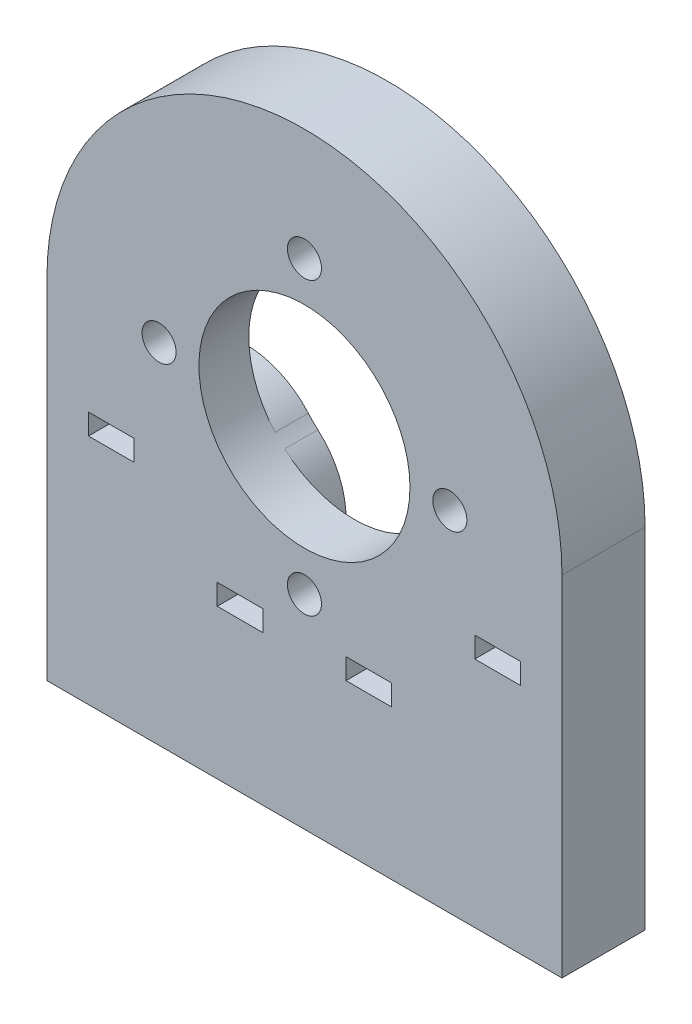
SolidWorks part; units mm, degrees
ref_plane "Front Plane" through (0, 0, 0) normal (1, 0, 0) x (0, 1, 0)
ref_plane "Top Plane" through (0, 0, 0) normal (0, 0, 1) x (0, 1, 0)
ref_plane "Right Plane" through (0, 0, 0) normal (0, 1, 0) x (-1, 0, 0)
sketch "Sketch1" plane through (0, 0, 0) normal (0, 0, 1) x (0, 1, 0)
  line L0 (0, 0) -> (42, 0) construction
  line L1 (0, 31) -> (0, -31)
  line L2 (0, 31) -> (42, 31)
  line L3 (0, -31) -> (42, -31)
  circle A0 centre (42, 0) radius 12.7021
  arc A1 (42, -31) -> (42, 31) centre (42, 0) ccw
  circle A2 centre (42, 0) radius 17.5
  circle A3 centre (59.5, 0) radius 2.05
  circle A4 centre (59.5, 0) radius 5
  circle A5 centre (42, -17.5) radius 5
  circle A6 centre (42, -17.5) radius 2.05
  circle A7 centre (24.5, 0) radius 5
  circle A8 centre (24.5, 0) radius 2.05
  circle A9 centre (42, 17.5) radius 5
  circle A10 centre (42, 17.5) radius 2.05
  point P7 (0, 0)
  dimension "D3" = 35
  dimension "D4" = 4.1
  dimension "D5" = 10
  dimension "D1" = 42
  dimension "D2" = 62
  dimension "D6" = 4
extrude "Boss-Extrude1" add sketch "Sketch1" along normal blind 10 contours L3 A1 L2 L1 A7 A2 A9 A4 A5 | L0 A7 A2 A8 | A8 L0 A2 | A7 L0 A8 A2 | L0 A8 A2 | A9 A2 A7 A0 | A10 A2 A9 A0 | A9 A0 A4 A2 | A2 A4 A0 A3 | A5 A2 A4 A0 | A6 A2 A5 A0 | A7 A2 A5 A0 | A6 A2 A5 | A2 A6 | A2 A6 | L0 A8 A2 A7 A0 | A2 L0 A8 | L0 A2 A8 | A8 L0 A0 A7 A2 | A2 A3 | A2 A3 | A2 A4 A3 | A2 A10 | A10 A2 A9 | A2 A10 region at (-2.4725, 22.2907, 0) region at (2.4725, 22.2907, 0) region at (-15.5, 0.9578, 0) region at (-0.8862, 23.6519, 0) region at (0.8862, 23.6519, 0) region at (-2.2829, 27.0064, 0) region at (-10.1867, 31.8133, 0) region at (10.1867, 31.8133, 0) region at (2.2829, 27.0064, 0) region at (-0.853, 25.3913, 0) region at (0.853, 25.3913, 0) region at (-19.7093, 42, 0) region at (-14.9936, 42, 0) region at (14.9936, 42, 0) region at (19.7093, 42, 0) region at (-18.3481, 42, 0) region at (-16.6087, 42, 0) region at (16.6087, 42, 0) region at (18.3481, 42, 0) region at (-10.1867, 52.1867, 0) region at (10.1867, 52.1867, 0) region at (0, 61.7093, 0) region at (0, 56.9936, 0) region at (0, 60.3481, 0) region at (0, 58.6087, 0)
extrude "Cut-Extrude1" cut sketch "Sketch1<3>" along normal blind 4 contours A7 | A9 | A4 | A5
sketch "Sketch1<3>" plane through (0, 0, 0) normal (0, 0, 1) x (0, 1, 0) same geometry as "Sketch1"
extrude "Cut-Extrude3" cut sketch "Sketch1<4>" along normal through all and the other way through all contours A6 | A3 | A10 | A8
sketch "Sketch1<4>" plane through (0, 0, 0) normal (0, 0, 1) x (0, 1, 0) same geometry as "Sketch1"
fillet "Fillet1" radius 10 8 edges at (-1.1976, 29.3545, 2) (1.1976, 29.3545, 2) (-12.6455, 40.8024, 2) (-12.6455, 43.1976, 2) (-1.1976, 54.6455, 2) (1.1976, 54.6455, 2) (12.6455, 43.1976, 2) (12.6455, 40.8024, 2)
sketch "Sketch2" plane through (0, 0, 0) normal (0, -1, 0) x (1, 0, 0)
  line L0 (-31, 5) -> (-23.25, 5) construction
  line L1 (-31, 10) -> (-31, 0) construction
  line L2 (-23.25, 5) -> (-23.25, 3.0468) construction
  line L3 (-22.3323, 3.6894) -> (-23.25, 3.0468)
  line L4 (-24.1677, 3.6894) -> (-23.25, 3.0468)
  line L5 (-8.6677, 3.6894) -> (-7.75, 3.0468)
  line L6 (-6.8323, 3.6894) -> (-7.75, 3.0468)
  line L7 (6.8323, 3.6894) -> (7.75, 3.0468)
  line L8 (8.6677, 3.6894) -> (7.75, 3.0468)
  line L9 (22.3323, 3.6894) -> (23.25, 3.0468)
  line L10 (24.1677, 3.6894) -> (23.25, 3.0468)
  arc A0 (-22.3323, 3.6894) -> (-24.1677, 3.6894) centre (-23.25, 5) ccw
  arc A1 (-6.8323, 3.6894) -> (-8.6677, 3.6894) centre (-7.75, 5) ccw
  arc A2 (8.6677, 3.6894) -> (6.8323, 3.6894) centre (7.75, 5) ccw
  arc A3 (24.1677, 3.6894) -> (22.3323, 3.6894) centre (23.25, 5) ccw
  point P4 (-23.25, 6.9532)
  point P8 (-22.9883, 3.0644)
  dimension "D2" = 3.2
  dimension "D1" = 7.75
  dimension "D3" = 55
  dimension "D4" = 4
sketch "Sketch3" plane through (0, 0, 10) normal (0, 0, 1) x (1, 0, 0)
  line L0 (-23.25, 28) -> (-23.25, 0)
  line L1 (-26, 30.5) -> (-20.5, 30.5)
  line L2 (-26, 30.5) -> (-26, 28)
  line L3 (-26, 28) -> (-20.5, 28)
  line L4 (-20.5, 30.5) -> (-20.5, 28)
  line L5 (-26, 30.5) -> (-20.5, 28) construction
  line L6 (-26, 28) -> (-20.5, 30.5) construction
  line L7 (-10.5, 20.5) -> (-5, 20.5)
  line L8 (-10.5, 20.5) -> (-10.5, 18)
  line L9 (-10.5, 18) -> (-5, 18)
  line L10 (-5, 20.5) -> (-5, 18)
  line L11 (-10.5, 20.5) -> (-5, 18) construction
  line L12 (-10.5, 18) -> (-5, 20.5) construction
  line L13 (5, 20.5) -> (10.5, 20.5)
  line L14 (5, 20.5) -> (5, 18)
  line L15 (5, 18) -> (10.5, 18)
  line L16 (10.5, 20.5) -> (10.5, 18)
  line L17 (5, 20.5) -> (10.5, 18) construction
  line L18 (5, 18) -> (10.5, 20.5) construction
  line L19 (20.5, 30.5) -> (26, 30.5)
  line L20 (20.5, 30.5) -> (20.5, 28)
  line L21 (20.5, 28) -> (26, 28)
  line L22 (26, 30.5) -> (26, 28)
  line L23 (20.5, 30.5) -> (26, 28) construction
  line L24 (20.5, 28) -> (26, 30.5) construction
  line L25 (-7.75, 18) -> (-7.75, 0)
  line L26 (7.75, 18) -> (7.75, 0)
  line L27 (23.25, 28) -> (23.25, 0)
  point P0 (23.25, 0)
  point P2 (7.75, 0)
  point P4 (-7.75, 0)
  point P6 (-23.25, 0)
  point P8 (-23.25, 29.25)
  point P13 (-7.75, 19.25)
  point P18 (7.75, 19.25)
  point P23 (23.25, 29.25)
  dimension "D1" = 5.5
  dimension "D2" = 5.5
  dimension "D3" = 5.5
  dimension "D4" = 5.5
  dimension "D5" = 2.5
  dimension "D6" = 2.5
  dimension "D7" = 2.5
  dimension "D8" = 2.5
  dimension "D9" = 28
  dimension "D10" = 18
extrude "Cut-Extrude12" cut sketch "Sketch3" against normal blind 2.75 and the other way through all from offset 5 contours L3 L4 L1 L2 | L22 L21 L20 L19 | L10 L9 L8 L7 | L14 L15 L16 L13 offset against normal yes
extrude "Cut-Extrude13" cut sketch "Sketch2" against normal offset from surface (31.5 mm away) 1 contours A0 L4 L3 | A3 L9 L10 up to face at (-23.25, 30.5, 6.125) offset beyond the face yes
extrude "Cut-Extrude14" cut sketch "Sketch2<3>" against normal offset from surface (21.5 mm away) 1 contours A1 L5 L6 | A2 L7 L8 up to face at (-7.75, 20.5, 6.125) offset beyond the face yes
sketch "Sketch2<3>" plane through (0, 0, 0) normal (0, -1, 0) x (1, 0, 0) same geometry as "Sketch2"
